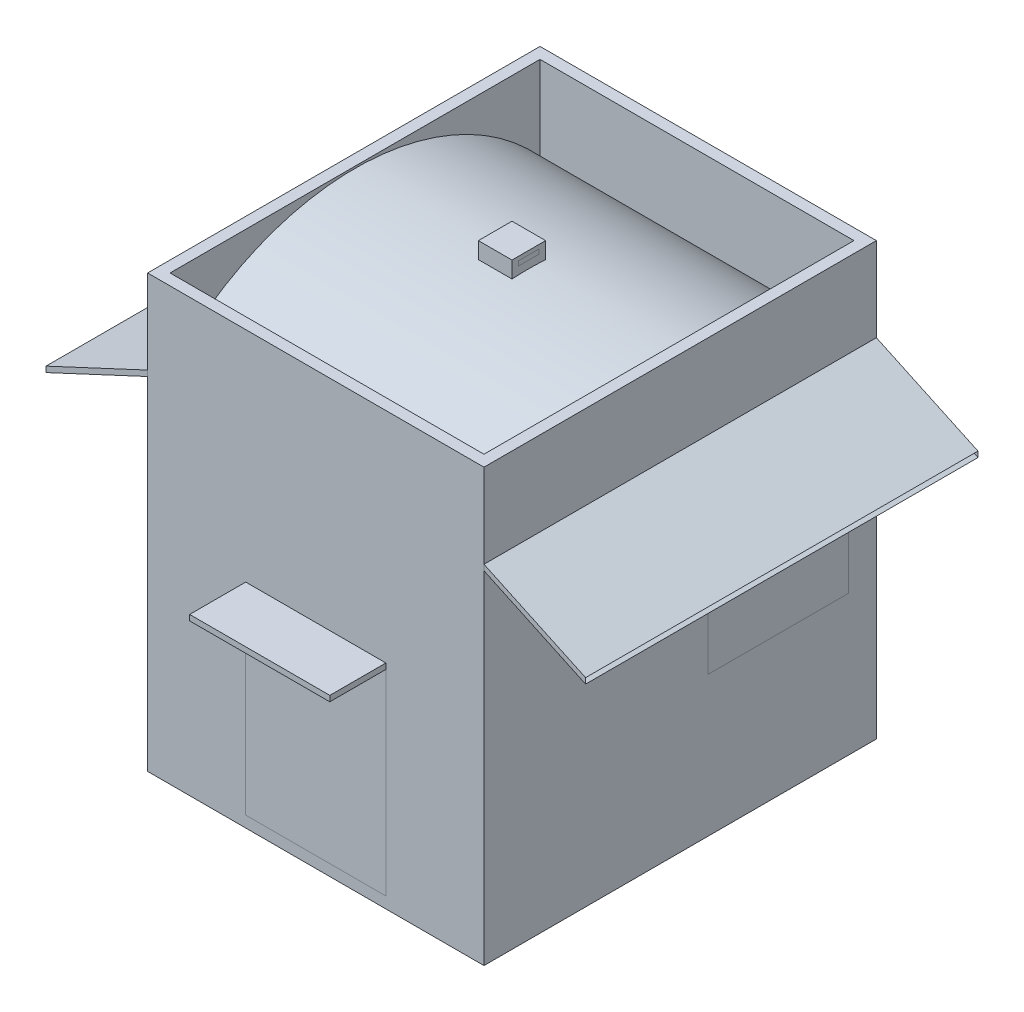
SolidWorks part; units mm, degrees
note: The reader was unsure of these and kept them because the rebuilt part matched: shared geometry of "Sketch16<2>", "Sketch28<5>", "Sketch28<6>", "Sketch28<7>".
ref_plane "Front Plane" through (0, 0, 0) normal (0, 0, 1) x (1, 0, 0)
ref_plane "Top Plane" through (0, 0, 0) normal (0, 1, 0) x (1, 0, 0)
ref_plane "Right Plane" through (0, 0, 0) normal (1, 0, 0) x (0, 0, -1)
sketch "Sketch16" plane through (0, 0, 0) normal (0, 1, 0) x (1, 0, 0)
  line L1 (-300, 350) -> (300, 350)
  line L2 (-300, 350) -> (-300, -350)
  line L3 (-300, -350) -> (300, -350)
  line L4 (300, 350) -> (300, -350)
  line L5 (-300, 350) -> (300, -350) construction
  line L6 (-300, -350) -> (300, 350) construction
  point P0 (0, 0)
  dimension "D1" = 700
  dimension "D2" = 600
extrude "Boss-Extrude1" add sketch "Sketch16" against normal blind 20
extrude "Boss-Extrude2" add sketch "Sketch16<2>" along normal blind 750
sketch "Sketch16<2>" plane through (0, 0, 0) normal (0, 1, 0) x (1, 0, 0) same geometry as "Sketch16"
shell "Shell1" thickness 20 removed face at (0, 750, 0)
ref_plane "Plane1" through (0, 0, 330) normal (0, 0, 1) x (1, 0, 0)
sketch "Sketch17" plane through (0, 0, 330) normal (0, 0, 1) x (1, 0, 0)
  line L0 (-300, -20) -> (-300, 750) construction
  line L1 (-280, 600) -> (280, 600)
  line L2 (-280, 600) -> (-280, 580)
  line L3 (-280, 580) -> (280, 580)
  line L4 (280, 600) -> (280, 580)
  line L7 (-300, 750) -> (300, 750) construction
  point P6 (280, 590)
  dimension "D1" = 20
  dimension "D2" = 560
  dimension "D3" = 160
  dimension "D4" = 20
sketch "Sketch18" plane through (0, 0, 0) normal (1, 0, 0) x (0, 0, -1)
  line L0 (-330, 590) -> (330, 590) construction
  line L1 (-330, 600) -> (-330, 580) construction
  line L2 (350, -20) -> (350, 750) construction
  arc A0 (-330, 590) -> (330, 590) centre (0, 302) cw
  point P7 (0, 740)
  dimension "D2" = 150
  dimension "D1" = 20
ref_plane "Plane3" through (0, 730, 0) normal (0, 1, 0) x (1, 0, 0)
sweep "Sweep1" add profiles "Sketch17" path "Sketch18"
sketch "Sketch28" plane through (-300, 0, 0) normal (-1, 0, 0) x (0, 0, 1)
  line L0 (0, 0) -> (0, 624.0916) construction
  line L1 (-350, -20) -> (-350, 750) construction
  line L2 (-250, 600) -> (-100, 600)
  line L3 (-250, 600) -> (-250, 580)
  line L4 (-250, 580) -> (-100, 580)
  line L5 (-100, 600) -> (-100, 580)
  line L6 (-350, 750) -> (350, 750) construction
  line L8 (100, 600) -> (100, 580)
  line L9 (250, 580) -> (100, 580)
  line L10 (250, 600) -> (250, 580)
  line L11 (250, 600) -> (100, 600)
  line L12 (-350, -20) -> (350, -20) construction
  line L13 (-300, 480) -> (-50, 480)
  line L14 (-300, 480) -> (-300, 230)
  line L15 (-300, 230) -> (-50, 230)
  line L16 (-50, 480) -> (-50, 230)
  line L17 (50, 480) -> (50, 230)
  line L18 (300, 230) -> (50, 230)
  line L19 (300, 480) -> (300, 230)
  line L20 (300, 480) -> (50, 480)
  dimension "D1" = 100
  dimension "D2" = 100
  dimension "D3" = 150
  dimension "D4" = 20
  dimension "D5" = 250
  dimension "D6" = 250
  dimension "D7" = 50
  dimension "D8" = 250
extrude "Cut-Extrude6" cut sketch "Sketch28" against normal through all contours L13 L16 L15 L14
extrude "Cut-Extrude7" cut sketch "Sketch28<5>" against normal blind 170 contours L20 L17 L18 L19
sketch "Sketch28<5>" plane through (-300, 0, 0) normal (-1, 0, 0) x (0, 0, 1) same geometry as "Sketch28"
extrude "Cut-Extrude8" cut sketch "Sketch28<6>" against normal through all contours L2 L5 L4 L3
sketch "Sketch28<6>" plane through (-300, 0, 0) normal (-1, 0, 0) x (0, 0, 1) same geometry as "Sketch28"
extrude "Cut-Extrude9" cut sketch "Sketch28<7>" against normal through all contours L9 L8 L11 L10
sketch "Sketch28<7>" plane through (-300, 0, 0) normal (-1, 0, 0) x (0, 0, 1) same geometry as "Sketch28"
sketch "Sketch30" plane through (0, 0, 350) normal (0, 0, 1) x (1, 0, 0)
  line L0 (-300, 600) -> (-481.2616, 515.4763)
  line L1 (-300, -20) -> (-300, 750) construction
  line L2 (-300, 750) -> (300, 750) construction
  dimension "D1" = 150
  dimension "D2" = 200
  dimension "D3" = 65
sketch "Sketch31" plane through (-300, 0, 0) normal (-1, 0, 0) x (0, 0, 1)
  line L0 (350, 600) -> (-350, 600)
  line L1 (350, 600) -> (350, 515.4763) construction
  line L2 (350, -20) -> (350, 750) construction
  line L3 (-350, -20) -> (-350, 750) construction
  line L4 (-350, 600) -> (-350, 590)
  line L5 (-350, 590) -> (350, 590)
  line L6 (350, 590) -> (350, 600)
  dimension "D1" = 10
  dimension "D2" = 700
surface "Surface-Sweep1"
sketch "Sketch35" plane through (0, 0, 350) normal (0, 0, 1) x (1, 0, 0)
  line L1 (0, 0) -> (0, 137.8874) construction
  line L2 (-125, 350) -> (125, 350)
  line L3 (-125, 350) -> (-125, 0)
  line L4 (-125, 0) -> (125, 0)
  line L5 (125, 350) -> (125, 0)
  line L6 (-300, -20) -> (300, -20) construction
  dimension "D1" = 250
  dimension "D2" = 350
  dimension "D3" = 20
extrude "Cut-Extrude10" cut sketch "Sketch35" against normal blind 170
sketch "Sketch36" plane through (0, 0, 350) normal (0, 0, 1) x (1, 0, 0)
  line L0 (-125, 0) -> (125, 0) construction
  line L1 (125, 350) -> (-125, 350)
  line L2 (125, 350) -> (125, 360)
  line L3 (125, 360) -> (-125, 360)
  line L4 (-125, 350) -> (-125, 360)
  dimension "D1" = 10
  dimension "D2" = 250
  dimension "D3" = 360
extrude "Boss-Extrude6" add sketch "Sketch36" along normal blind 100
sketch "Sketch41" plane through (300, 0, 0) normal (1, 0, 0) x (0, 0, -1)
  line L0 (-350, 600) -> (350, 600)
  line L1 (350, -20) -> (350, 750) construction
  line L2 (350, 600) -> (350, 590)
  line L4 (350, 590) -> (-350, 590)
  line L5 (-350, 590) -> (-350, 600)
sketch "Sketch43" plane through (0, 0, 350) normal (0, 0, 1) x (1, 0, 0)
  line L0 (300, 600) -> (481.2616, 515.4763)
  line L1 (300, -20) -> (300, 750) construction
  line L2 (-300, 750) -> (300, 750) construction
  dimension "D1" = 65
  dimension "D2" = 200
  dimension "D3" = 150
surface "Surface-Sweep2"
sketch "Sketch45" plane through (0, 730, 0) normal (0, 1, 0) x (1, 0, 0)
  line L1 (-30, 30) -> (30, 30)
  line L2 (-30, 30) -> (-30, -30)
  line L3 (-30, -30) -> (30, -30)
  line L4 (30, 30) -> (30, -30)
  line L5 (-30, 30) -> (30, -30) construction
  line L6 (-30, -30) -> (30, 30) construction
  point P0 (0, 0)
  dimension "D1" = 60
  dimension "D2" = 60
extrude "Boss-Extrude7" add sketch "Sketch45" along normal blind 40
sketch "Sketch46" plane through (0, 730, 0) normal (0, 1, 0) x (1, 0, 0)
  line L1 (-25, 25) -> (25, 25)
  line L2 (-25, 25) -> (-25, -25)
  line L3 (-25, -25) -> (25, -25)
  line L4 (25, 25) -> (25, -25)
  line L5 (-25, 25) -> (25, -25) construction
  line L6 (-25, -25) -> (25, 25) construction
  point P1 (0, 0)
  dimension "D1" = 50
  dimension "D2" = 50
extrude "Cut-Extrude12" cut sketch "Sketch46" along normal blind 30
sketch "Sketch47" plane through (0, 770, 0) normal (0, 1, 0) x (1, 0, 0)
  line L1 (-30, 30) -> (30, 30)
  line L2 (-30, 30) -> (-30, -30)
  line L3 (-30, -30) -> (30, -30)
  line L4 (30, 30) -> (30, -30)
extrude "Boss-Extrude8" add sketch "Sketch47" along normal blind 5
sketch "Sketch48" plane through (30, 0, 0) normal (1, 0, 0) x (0, 0, -1)
  line L0 (0, 775) -> (0, 766.4574) construction
  line L1 (-18, 768) -> (18, 768)
  line L2 (-18, 768) -> (-18, 760)
  line L3 (-18, 760) -> (18, 760)
  line L4 (18, 768) -> (18, 760)
  line L5 (-30, 775) -> (30, 775) construction
  line L6 (-350, 750) -> (350, 750) construction
  line L8 (30, 775) -> (30, 745.626) construction
  point P9 (0, 768)
  dimension "D1" = 8
  dimension "D2" = 10
  dimension "D3" = 12
extrude "Cut-Extrude13" cut sketch "Sketch48" against normal blind 63
sketch "Sketch49" plane through (125, 0, 0) normal (-1, 0, 0) x (0, 0, 1)
  line L0 (330, 0) -> (350, 0) construction
  line L1 (330, 350) -> (350, 350) construction
  line L2 (330, 0) -> (330, 350) construction
  line L3 (350, 0) -> (350, 350) construction
  line L4 (330, 0) -> (350, 0)
  line L5 (330, 350) -> (350, 350)
  line L6 (330, 0) -> (330, 350)
  line L7 (350, 0) -> (350, 350)
extrude "Boss-Extrude10" add sketch "Sketch49" along normal up to surface (250 mm away) separate body up to face at (-125, 175, 340)
sketch "Sketch50" plane through (0, 0, -300) normal (0, 0, 1) x (1, 0, 0)
  line L0 (300, 230) -> (280, 230) construction
  line L1 (300, 480) -> (280, 480) construction
  line L2 (280, 230) -> (280, 480) construction
  line L3 (300, 480) -> (300, 230) construction
  line L4 (300, 230) -> (280, 230)
  line L5 (300, 480) -> (280, 480)
  line L6 (280, 230) -> (280, 480)
  line L7 (300, 480) -> (300, 230)
extrude "Boss-Extrude11" add sketch "Sketch50" along normal up to surface (250 mm away) separate body up to face at (290, 355, -50)
sketch "Sketch52" plane through (0, 0, 300) normal (0, 0, -1) x (-1, 0, 0)
  line L0 (280, 480) -> (300, 480) construction
  line L1 (280, 230) -> (300, 230) construction
  line L2 (300, 480) -> (300, 230) construction
  line L3 (280, 480) -> (280, 230) construction
  line L4 (280, 480) -> (300, 480)
  line L5 (280, 230) -> (300, 230)
  line L6 (300, 480) -> (300, 230)
  line L7 (280, 480) -> (280, 230)
extrude "Boss-Extrude12" add sketch "Sketch52" along normal up to surface (250 mm away) separate body up to face at (-290, 355, 50)
sketch "Sketch53" plane through (0, 0, -300) normal (0, 0, 1) x (1, 0, 0)
  line L0 (-280, 480) -> (-300, 480) construction
  line L1 (-280, 230) -> (-300, 230) construction
  line L2 (-280, 480) -> (-280, 230) construction
  line L3 (-300, 480) -> (-300, 230) construction
  line L4 (-280, 480) -> (-300, 480)
  line L5 (-280, 230) -> (-300, 230)
  line L6 (-280, 480) -> (-280, 230)
  line L7 (-300, 480) -> (-300, 230)
extrude "Boss-Extrude13" add sketch "Sketch53" along normal up to surface (250 mm away) separate body up to face at (290, 355, -50)
sketch "Sketch54" plane through (-30, 0, 0) normal (-1, 0, 0) x (0, 0, 1)
  line L0 (-18, 760) -> (-18, 768) construction
  line L1 (18, 760) -> (-18, 760) construction
  line L2 (18, 768) -> (18, 760) construction
  line L3 (-18, 768) -> (18, 768) construction
  line L4 (-18, 760) -> (-18, 768)
  line L5 (18, 760) -> (-18, 760)
  line L6 (18, 768) -> (18, 760)
  line L7 (-18, 768) -> (18, 768)
extrude "Boss-Extrude14" add sketch "Sketch54" against normal up to surface (60 mm away) separate body up to face at (30, 731.4842, 0)
sketch "Sketch55" plane through (-280, 0, 0) normal (1, 0, 0) x (0, 0, -1)
  line L0 (250, 600) -> (250, 580) construction
  line L1 (250, 580) -> (100, 580) construction
  line L2 (250, 600) -> (100, 600) construction
  line L3 (100, 600) -> (100, 580) construction
  line L4 (-100, 600) -> (-100, 580) construction
  line L5 (-250, 600) -> (-100, 600) construction
  line L6 (-250, 580) -> (-100, 580) construction
  line L7 (-250, 600) -> (-250, 580) construction
  line L8 (250, 600) -> (250, 580)
  line L9 (250, 580) -> (100, 580)
  line L10 (250, 600) -> (100, 600)
  line L11 (100, 600) -> (100, 580)
  line L12 (-100, 600) -> (-100, 580)
  line L13 (-250, 600) -> (-100, 600)
  line L14 (-250, 580) -> (-100, 580)
  line L15 (-250, 600) -> (-250, 580)
extrude "Boss-Extrude15" add sketch "Sketch55" along a picked direction on the side against the normal up to surface (20 mm away) separate body
sketch "Sketch56" plane through (300, 0, 0) normal (1, 0, 0) x (0, 0, -1)
  line L0 (100, 600) -> (100, 580) construction
  line L1 (250, 600) -> (100, 600) construction
  line L2 (250, 600) -> (250, 580) construction
  line L3 (250, 580) -> (100, 580) construction
  line L4 (-250, 600) -> (-100, 600) construction
  line L5 (-100, 600) -> (-100, 580) construction
  line L6 (-250, 580) -> (-100, 580) construction
  line L7 (-250, 600) -> (-250, 580) construction
  line L8 (100, 600) -> (100, 580)
  line L9 (250, 600) -> (100, 600)
  line L10 (250, 600) -> (250, 580)
  line L11 (250, 580) -> (100, 580)
  line L12 (-250, 600) -> (-100, 600)
  line L13 (-100, 600) -> (-100, 580)
  line L14 (-250, 580) -> (-100, 580)
  line L15 (-250, 600) -> (-250, 580)
extrude "Boss-Extrude16" add sketch "Sketch56" against normal up to surface (20 mm away) separate body
